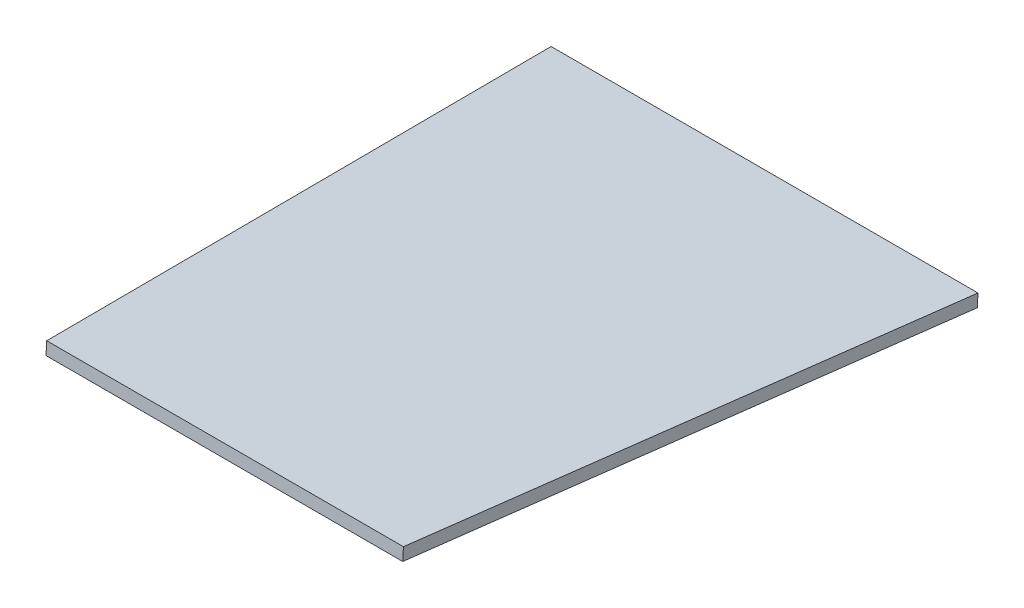
SolidWorks part; units mm, degrees
ref_plane "Front Plane" through (0, 0, 0) normal (0, 0, 1) x (1, 0, 0)
ref_plane "Top Plane" through (0, 0, 0) normal (0, 1, 0) x (1, 0, 0)
ref_plane "Right Plane" through (0, 0, 0) normal (1, 0, 0) x (0, 0, -1)
ref_plane "Pedlabox Floor Plane" through (0, -11.9121, 0.7164) normal (0, -0.9982, 0.06) x (-1, 0, 0)
sketch "PedalBox Floor" plane through (0, -11.9121, 0.7164) normal (0, -0.9982, 0.06) x (-1, 0, 0)
  line L0 (349.5084, -1328.8525) -> (385.2316, -1878.7214)
  line L1 (385.2316, -1878.7214) -> (748.1684, -1878.7214)
  line L2 (748.1684, -1878.7214) -> (783.8915, -1328.8525)
  line L3 (783.8915, -1328.8525) -> (349.5084, -1328.8525)
  line L4 (754.3712, -1328.8525) -> (379.0287, -1328.8525) construction
  line L9 (748.5134, -1873.4105) -> (796.6296, -1132.7821) construction
  line L10 (336.7704, -1132.7821) -> (384.8865, -1873.4105) construction
  line L11 (748.31, -1878.7214) -> (385.09, -1878.7214) construction
extrude "Boss-Extrude1" add sketch "PedalBox Floor" along normal blind 12.7 contours L3 L0 L1 L2
